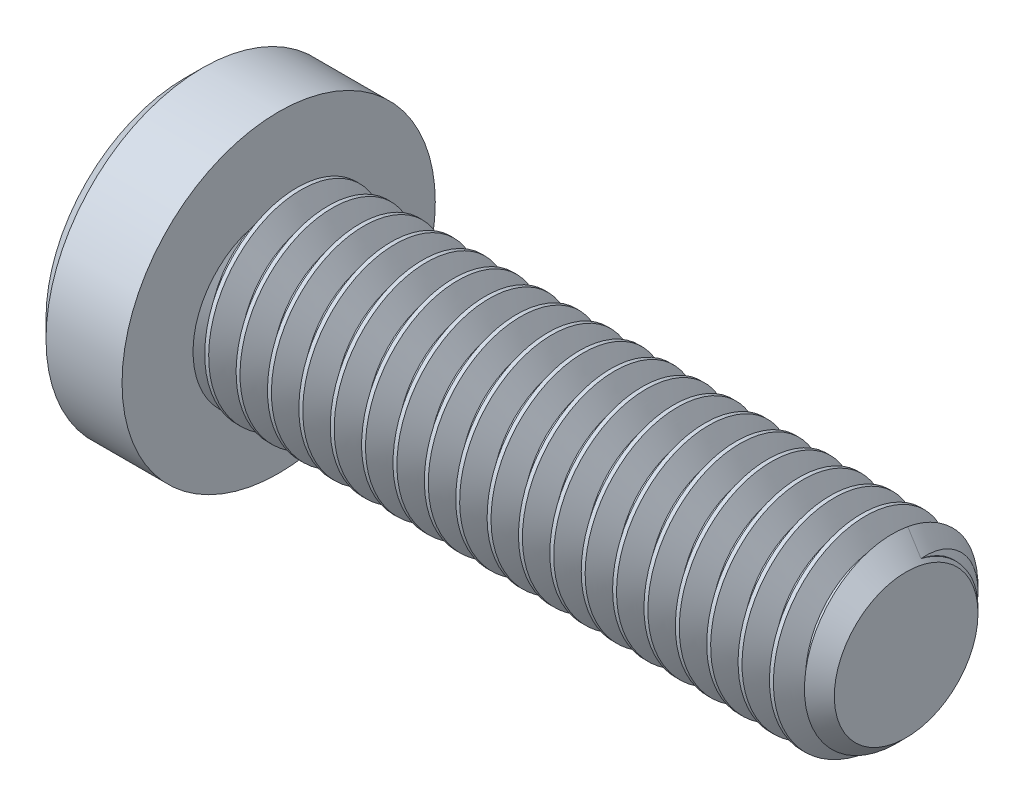
SolidWorks part; units mm, degrees
ref_plane "Front Plane" through (0, 0, 0) normal (0, 0, 1) x (1, 0, 0)
ref_plane "Top Plane" through (0, 0, 0) normal (0, 1, 0) x (1, 0, 0)
ref_plane "Right Plane" through (0, 0, 0) normal (1, 0, 0) x (0, 0, -1)
sketch "Sketch1" plane through (0, 0, 0) normal (0, 0, 1) x (1, 0, 0)
  line L0 (7.9375, 0) -> (-7.9375, 0) construction
  line L1 (7.9375, 2.413) -> (7.9375, -2.413) construction
  line L2 (-7.9375, 3.9624) -> (-7.9375, -3.9624) construction
  line L3 (-7.9375, 3.9624) -> (-9.8615, 3.9624) construction
  line L4 (-9.8615, 3.9624) -> (-10.3187, 3.5052) construction
  line L5 (-10.3187, 3.5052) -> (-10.3187, -3.5052) construction
  line L6 (-10.3187, -3.5052) -> (-9.8615, -3.9624) construction
  line L7 (-9.8615, -3.9624) -> (-7.9375, -3.9624) construction
  point P7 (-8.49, 0)
  point P12 (4.7625, -2.413)
  dimension "D1" = 45
  dimension "Dec." = 4.826
  dimension "Length" = 15.875
  dimension "Head Dia" = 7.9248
  dimension "Head Height" = 2.3813
  dimension "Hex Depth" = 1.8288
  dimension "Chamfer" = 0.4572
  dimension "D2" = 3.175
ref_plane "Plane1" through (7.9375, 0, 0) normal (1, 0, 0) x (0, 0, -1)
ref_plane "Plane2" through (-10.3187, 0, 0) normal (1, 0, 0) x (0, 0, -1)
sketch "Sketch2" plane through (7.9375, 0, 0) normal (1, 0, 0) x (0, 0, -1)
  circle A0 centre (0, 0) radius 2.413
extrude "Boss-Extrude1" add sketch "Sketch2" against normal up to vertex (15.875 mm away) up to point (-7.9375, 0, 0)
sketch "Sketch3" plane through (7.9375, 0, 0) normal (1, 0, 0) x (0, 0, -1)
  circle A0 centre (0, 0) radius 2.413 construction
  circle A1 centre (0, 0) radius 2.413
curve "Helix/Spiral1" pitch 0.7937 height 16.6687 radius 2.413 centre (7.9375, 0, 0) axis (-1, 0, 0) start towards (0, 1, 0) parameters "Pitch"=0.7937
chamfer "Chamfer1" distance 0.5953 angle 45 1 edges at (7.9375, 0, -2.413)
sketch "Sketch5" plane through (0, 0, 0) normal (0, 0, 1) x (1, 0, 0)
  line L0 (7.5902, 2.413) -> (8.2848, 2.413)
  line L1 (8.2848, 2.413) -> (7.9871, 1.8974)
  line L2 (7.9871, 1.8974) -> (7.8879, 1.8974)
  line L3 (7.8879, 1.8974) -> (7.5902, 2.413)
  line L4 (7.9375, 1.8974) -> (7.9375, 2.413) construction
  line L5 (7.7391, 2.1552) -> (8.1359, 2.1552) construction
  dimension "D1" = 60
  dimension "D2" = 0.3969
  dimension "D3" = 0.0992
sweep "Cut-Sweep1" cut profiles "Sketch5" path "Helix/Spiral1" align with end faces yes
sketch "Sketch4" plane through (-10.3187, 0, 0) normal (1, 0, 0) x (0, 0, -1)
  line L0 (-3.9624, 0.7937) -> (3.9624, 0.7937) construction
  line L1 (0, 1.3748) -> (-1.1906, 0.6874)
  line L2 (-1.1906, 0.6874) -> (-1.1906, -0.6874)
  line L3 (-1.1906, -0.6874) -> (0, -1.3748)
  line L4 (0, -1.3748) -> (1.1906, -0.6874)
  line L5 (1.1906, -0.6874) -> (1.1906, 0.6874)
  line L6 (1.1906, 0.6874) -> (0, 1.3748)
  line L7 (0, 0) -> (0, 0.7937) construction
  circle A0 centre (0, 0) radius 1.1906 construction
  dimension "Hex Size" = 2.3813
  dimension "D1" = 7.9248
  dimension "D2" = 0.7937
sketch "Sketch6" plane through (0, 0, 0) normal (0, 0, 1) x (1, 0, 0)
  line L0 (-9.8615, 3.9624) -> (-10.3187, 3.5052) construction
  line L1 (-7.9375, 3.9624) -> (-9.8615, 3.9624) construction
  line L2 (-7.9375, 3.9624) -> (-7.9375, -3.9624) construction
  line L3 (-10.3187, 3.5052) -> (-10.3187, -3.5052) construction
  line L4 (-9.8615, 3.9624) -> (-10.3187, 3.5052)
  line L5 (-7.9375, 3.9624) -> (-9.8615, 3.9624)
  line L6 (-7.9375, 3.9624) -> (-7.9375, 0)
  line L7 (-10.3187, 3.5052) -> (-10.3187, 0)
  line L8 (-7.9375, 0) -> (-10.3187, 0) construction
  line L9 (-7.9375, 0) -> (-10.3187, 0)
revolve "Revolve1" add sketch "Sketch6" angle 360 about L8
extrude "Cut-Extrude1" cut sketch "Sketch4" along normal up to vertex (1.8288 mm away) up to point (-8.49, 0, 0)
sketch "Sketch8" plane through (-10.3187, 0, 0) normal (-1, 0, 0) x (0, 0, 1)
  circle A1 centre (0, 0) radius 1.3748
extrude "Cut-Extrude2" cut sketch "Sketch8" against normal through all draft 45
equation "\"D3@Helix/Spiral1\" = \"Length@Sketch1\"+\"Pitch@Helix/Spiral1\""
equation "\"D3@Sketch5\" = \"Pitch@Helix/Spiral1\"*.125"
equation "\"D2@Sketch5\" = \"Pitch@Helix/Spiral1\"*.50"
equation "\"D1@Chamfer1\" = \"Pitch@Helix/Spiral1\"*.75"
equation "\"D2@Sketch1\" = \"Pitch@Helix/Spiral1\"*4"
equation "\"D1@Sketch4\" = \"Head Dia@Sketch1\""
